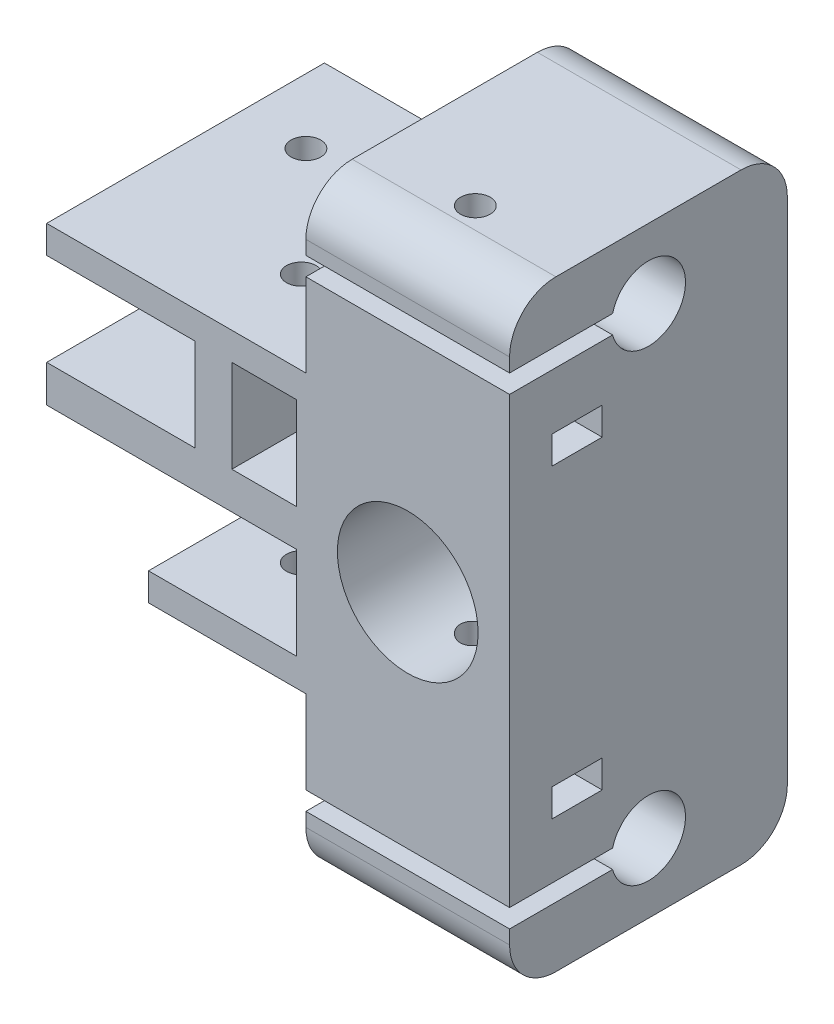
SolidWorks part; units mm, degrees
ref_plane "Plano frontal" through (0, 0, 0) normal (0, 0, 1) x (1, 0, 0)
ref_plane "Plano superior" through (0, 0, 0) normal (0, 1, 0) x (1, 0, 0)
ref_plane "Plano direito" through (0, 0, 0) normal (1, 0, 0) x (0, 0, -1)
sketch "Esboço2" plane through (0, 0, 0) normal (0, 0, 1) x (1, 0, 0)
  line L0 (-11, 15) -> (-11, 32.5)
  line L1 (-11, -32.5) -> (11, -32.5)
  line L2 (-11, -32.5) -> (-11, -15)
  line L3 (-11, 32.5) -> (11, 32.5)
  line L4 (11, -32.5) -> (11, 32.5)
  line L5 (-11, -32.5) -> (11, 32.5) construction
  line L6 (-11, 32.5) -> (11, -32.5) construction
  line L7 (-39, 15) -> (-11, 15)
  line L8 (-39, 15) -> (-39, 12)
  line L9 (-28, -15) -> (-11, -15)
  line L10 (0, 0) -> (-50.7474, 0) construction
  line L11 (-39, 15) -> (-11, -15) construction
  line L12 (-39, -15) -> (-11, 15) construction
  line L13 (-19, 2) -> (-12, 2)
  line L14 (-19, 2) -> (-19, 12)
  line L15 (-19, 12) -> (-12, 12)
  line L16 (-12, 2) -> (-12, 12)
  line L17 (-19, 2) -> (-12, 12) construction
  line L18 (-19, 12) -> (-12, 2) construction
  line L19 (-23, 12) -> (-39, 12)
  line L20 (-23, 12) -> (-23, 2)
  line L21 (-23, 2) -> (-39, 2)
  line L22 (-39, -2) -> (-28, -2)
  line L23 (-23, 12) -> (-39, 2) construction
  line L24 (-23, 2) -> (-39, 12) construction
  line L25 (-12, -2) -> (-28, -2)
  line L26 (-12, -2) -> (-12, -12)
  line L27 (-12, -12) -> (-28, -12)
  line L29 (-28, -12) -> (-28, -15)
  line L31 (-39, 2) -> (-39, -2)
  line L33 (-12, -2) -> (-28, -12) construction
  line L34 (-12, -12) -> (-28, -2) construction
  circle A0 centre (0, 0) radius 7.6
  point P7 (-25, 0)
  point P12 (-15.5, 7)
  point P18 (-31, 7)
  point P26 (-20, -7)
  dimension "D1" = 15.2
  dimension "D2" = 65
  dimension "D3" = 22
  dimension "D4" = 30
  dimension "D5" = 28
  dimension "D6" = 3
  dimension "D7" = 7
  dimension "D8" = 23
  dimension "D9" = 16
  dimension "D10" = 1
  dimension "D11" = 10
  dimension "D12" = 3
  dimension "D13" = 17
extrude "Ressalto-extrusão1" add sketch "Esboço2" along normal blind 30
sketch "Esboço3" plane through (-11, 0, 0) normal (-1, 0, 0) x (0, 0, 1)
  line L0 (0, 0) -> (30, 0) construction
  line L3 (30, 32.5) -> (30, 15) construction
  line L5 (20, 18) -> (25.4, 18)
  line L6 (20, 18) -> (20, 15)
  line L7 (20, 15) -> (25.4, 15)
  line L8 (25.4, 18) -> (25.4, 15)
  line L9 (20, 18) -> (25.4, 15) construction
  line L10 (20, 15) -> (25.4, 18) construction
  line L11 (30, 15) -> (0, 15) construction
  line L12 (19.6387, 25) -> (32.742, 25) construction
  line L13 (18.873, 24) -> (32.742, 24)
  line L14 (18.873, 26) -> (32.742, 26)
  line L15 (15, 26) -> (32.742, 26) construction
  line L16 (15, 25) -> (32.742, 25) construction
  line L17 (15, 24) -> (32.742, 24) construction
  line L18 (32.742, 24) -> (32.742, 26)
  line L19 (19.6387, -25) -> (32.742, -25) construction
  line L20 (20, -15) -> (25.4, -18) construction
  line L21 (20, -18) -> (25.4, -15) construction
  line L22 (32.742, -24) -> (32.742, -26)
  line L23 (18.873, -26) -> (32.742, -26)
  line L24 (18.873, -24) -> (32.742, -24)
  line L25 (25.4, -18) -> (25.4, -15)
  line L26 (20, -15) -> (25.4, -15)
  line L27 (20, -18) -> (20, -15)
  line L28 (20, -18) -> (25.4, -18)
  line L29 (30, 32.5) -> (0, 32.5) construction
  arc A0 (18.873, 26) -> (18.873, 24) centre (15, 25) ccw
  arc A1 (18.873, -26) -> (18.873, -24) centre (15, -25) cw
  point P11 (22.7, 16.5)
  point P33 (22.7, -16.5)
  point P37 (15, 32.5)
  dimension "D1" = 4
  dimension "D2" = 50
  dimension "D3" = 5.4
  dimension "D4" = 5
  dimension "D5" = 3
  dimension "D6" = 1
  dimension "D7" = 1
extrude "Corte-extrusão1" cut sketch "Esboço3" against normal through all
sketch "Esboço4" plane through (0, 15, 0) normal (0, 1, 0) x (1, 0, 0)
  line L0 (-39, -30) -> (-39, 0) construction
  line L3 (-11, -30) -> (-11, 0) construction
  line L4 (-11, -30) -> (-11, -25.4) construction
  circle A0 centre (-32, -9) radius 1.6
  circle A1 centre (-32, -9) radius 5 construction
  circle A2 centre (-32, -9) radius 7 construction
  circle A3 centre (-20.5, -21) radius 1.6
  point P9 (-11, -15)
  dimension "D2" = 14
  dimension "D3" = 6
  dimension "D1" = 3.2
  dimension "D5" = 10
  dimension "D4" = 7
  dimension "D6" = 9.5
  dimension "D7" = 6
extrude "Corte-extrusão2" cut sketch "Esboço4" against normal through all both and the other way through all
sketch "Esboço5" plane through (0, 32.5, 0) normal (0, 1, 0) x (1, 0, 0)
  line L1 (11, -30) -> (-11, -30) construction
  line L2 (11, 0) -> (-11, 0) construction
  circle A0 centre (0, -22.7) radius 1.6
  point P8 (0, 0)
  dimension "D2" = 3.2
  dimension "D1" = 7.3
extrude "Corte-extrusão3" cut sketch "Esboço5" against normal through all both and the other way through all
fillet "Filete1" radius 5 4 edges at (0, -32.5, 30) (0, -32.5, 0) (0, 32.5, 30) (0, 32.5, 0)
